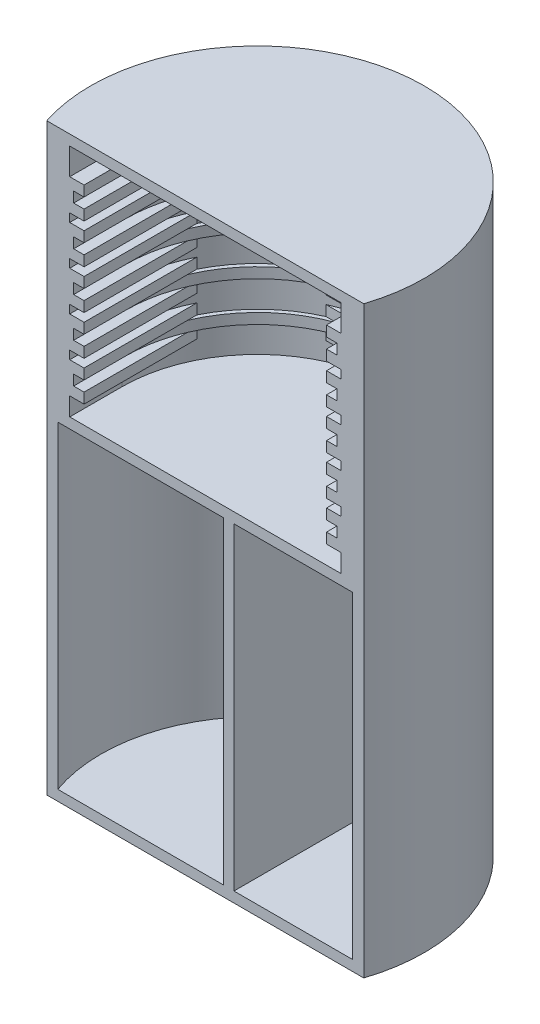
SolidWorks part; units mm, degrees
ref_plane "Front Plane" through (0, 0, 0) normal (0, 0, 1) x (1, 0, 0)
ref_plane "Top Plane" through (0, 0, 0) normal (0, 1, 0) x (1, 0, 0)
ref_plane "Right Plane" through (0, 0, 0) normal (1, 0, 0) x (0, 0, -1)
ref_plane "HYDRA SECTION TOP" through (0, 22.5, 0) normal (0, 1, 0) x (1, 0, 0)
ref_plane "HYDRA SECTION BOTTOM" through (0, -22.5, 0) normal (0, 1, 0) x (1, 0, 0)
ref_plane "BATTERY SECTION BOTTOM" through (0, -87.5, 0) normal (0, 1, 0) x (1, 0, 0)
sketch "Sketch1" plane through (0, 0, 0) normal (0, 1, 0) x (1, 0, 0)
  line L0 (-26, 0) -> (-26, -10)
  line L1 (26, 0) -> (26, -10)
  line L2 (-26, -10) -> (-30.3974, -10)
  line L3 (26, -10) -> (30.3974, -10)
  arc A0 (26, 0) -> (-26, 0) centre (0, 0) ccw
  arc A1 (30.3974, -10) -> (-30.3974, -10) centre (0, 0) ccw
  circle A2 centre (0, 0) radius 32 construction
  circle A3 centre (0, 0) radius 26 construction
  dimension "D1" = 52
  dimension "D2" = 64
  dimension "D3" = 10
extrude "BULK EXTRUDE" add sketch "Sketch1" along normal up to surface (22.5 mm away) and the other way up to surface (22.5 mm away) up to plane "HYDRA SECTION TOP" other way up to plane "HYDRA SECTION BOTTOM"
sketch "Sketch3" plane through (0, 0, 0) normal (0, 0, 1) x (1, 0, 0)
  line L0 (-25.25, 0.2) -> (-23.25, 0.2)
  line L1 (-23.25, 0.2) -> (-23.25, 2.2)
  line L2 (-23.25, 2.2) -> (-26.25, 2.2)
  line L3 (-26.25, 2.2) -> (-26.25, -3.8)
  line L4 (-26.25, -3.8) -> (-23.25, -3.8)
  line L5 (-23.25, -3.8) -> (-23.25, -1.8)
  line L6 (-23.25, -1.8) -> (-25.25, -1.8)
  line L7 (-25.25, -1.8) -> (-25.25, 0.2)
  line L8 (-26.25, -0.8) -> (-25.25, -0.8) construction
  line L9 (0, -23.1) -> (0, 23.1) construction
  line L10 (25.25, -1.8) -> (25.25, 0.2)
  line L11 (23.25, -1.8) -> (25.25, -1.8)
  line L12 (23.25, -3.8) -> (23.25, -1.8)
  line L13 (26.25, -3.8) -> (23.25, -3.8)
  line L14 (26.25, 2.2) -> (26.25, -3.8)
  line L15 (23.25, 2.2) -> (26.25, 2.2)
  line L16 (23.25, 0.2) -> (23.25, 2.2)
  line L17 (25.25, 0.2) -> (23.25, 0.2)
  line L18 (-25.25, 7.8) -> (-23.25, 7.8)
  line L19 (-23.25, 7.8) -> (-23.25, 9.8)
  line L20 (-23.25, 9.8) -> (-26.25, 9.8)
  line L21 (-26.25, 9.8) -> (-26.25, 3.8)
  line L22 (-26.25, 3.8) -> (-23.25, 3.8)
  line L23 (-23.25, 3.8) -> (-23.25, 5.8)
  line L24 (-23.25, 5.8) -> (-25.25, 5.8)
  line L25 (-25.25, 5.8) -> (-25.25, 7.8)
  line L26 (25.25, 5.8) -> (25.25, 7.8)
  line L27 (25.25, 7.8) -> (23.25, 7.8)
  line L28 (23.25, 7.8) -> (23.25, 9.8)
  line L29 (23.25, 9.8) -> (26.25, 9.8)
  line L30 (26.25, 9.8) -> (26.25, 3.8)
  line L31 (26.25, 3.8) -> (23.25, 3.8)
  line L32 (23.25, 3.8) -> (23.25, 5.8)
  line L33 (23.25, 5.8) -> (25.25, 5.8)
  line L34 (-25.25, 15.4) -> (-23.25, 15.4)
  line L35 (-23.25, 15.4) -> (-23.25, 17.4)
  line L36 (-23.25, 17.4) -> (-26.25, 17.4)
  line L37 (-26.25, 17.4) -> (-26.25, 11.4)
  line L38 (-26.25, 11.4) -> (-23.25, 11.4)
  line L39 (-23.25, 11.4) -> (-23.25, 13.4)
  line L40 (-23.25, 13.4) -> (-25.25, 13.4)
  line L41 (-25.25, 13.4) -> (-25.25, 15.4)
  line L42 (25.25, 13.4) -> (25.25, 15.4)
  line L43 (25.25, 15.4) -> (23.25, 15.4)
  line L44 (23.25, 15.4) -> (23.25, 17.4)
  line L45 (23.25, 17.4) -> (26.25, 17.4)
  line L46 (26.25, 17.4) -> (26.25, 11.4)
  line L47 (26.25, 11.4) -> (23.25, 11.4)
  line L48 (23.25, 11.4) -> (23.25, 13.4)
  line L49 (23.25, 13.4) -> (25.25, 13.4)
  line L50 (-25.25, -7.4) -> (-23.25, -7.4)
  line L51 (-23.25, -7.4) -> (-23.25, -5.4)
  line L52 (-23.25, -5.4) -> (-26.25, -5.4)
  line L53 (-26.25, -5.4) -> (-26.25, -11.4)
  line L54 (-26.25, -11.4) -> (-23.25, -11.4)
  line L55 (-23.25, -11.4) -> (-23.25, -9.4)
  line L56 (-23.25, -9.4) -> (-25.25, -9.4)
  line L57 (-25.25, -9.4) -> (-25.25, -7.4)
  line L58 (25.25, -9.4) -> (25.25, -7.4)
  line L59 (25.25, -7.4) -> (23.25, -7.4)
  line L60 (23.25, -7.4) -> (23.25, -5.4)
  line L61 (23.25, -5.4) -> (26.25, -5.4)
  line L62 (26.25, -5.4) -> (26.25, -11.4)
  line L63 (26.25, -11.4) -> (23.25, -11.4)
  line L64 (23.25, -11.4) -> (23.25, -9.4)
  line L65 (23.25, -9.4) -> (25.25, -9.4)
  line L66 (-25.25, -15) -> (-23.25, -15)
  line L67 (-23.25, -15) -> (-23.25, -13)
  line L68 (-23.25, -13) -> (-26.25, -13)
  line L69 (-26.25, -13) -> (-26.25, -19)
  line L70 (-26.25, -19) -> (-23.25, -19)
  line L71 (-23.25, -19) -> (-23.25, -17)
  line L72 (-23.25, -17) -> (-25.25, -17)
  line L73 (-25.25, -17) -> (-25.25, -15)
  line L74 (25.25, -17) -> (25.25, -15)
  line L75 (25.25, -15) -> (23.25, -15)
  line L76 (23.25, -15) -> (23.25, -13)
  line L77 (23.25, -13) -> (26.25, -13)
  line L78 (26.25, -13) -> (26.25, -19)
  line L79 (26.25, -19) -> (23.25, -19)
  line L80 (23.25, -19) -> (23.25, -17)
  line L81 (23.25, -17) -> (25.25, -17)
  dimension "D1" = 23.25
  dimension "D2" = 2
  dimension "D3" = 2
  dimension "D4" = 6
  dimension "D5" = 1
  dimension "D8" = 7.6
  dimension "D9" = 7.6
  dimension "D10" = 0.8
  dimension "D6" = 3
  dimension "D7" = 3
extrude "SIDE CRADDLES" add sketch "Sketch3" along normal blind 10 and the other way up to surface other way up to face at (0, 0, -13)
sketch "Sketch5" plane through (0, 0, 0) normal (1, 0, 0) x (0, 0, -1)
  line L0 (23.75, 2.2) -> (23.75, 0.2)
  line L1 (23.75, 0.2) -> (25.25, 0.2)
  line L2 (25.25, 0.2) -> (25.25, -1.8)
  line L3 (25.25, -1.8) -> (23.75, -1.8)
  line L4 (23.75, -1.8) -> (23.75, -3.8)
  line L5 (23.75, -3.8) -> (26.25, -3.8)
  line L6 (26.25, -3.8) -> (26.25, 2.2)
  line L7 (26.25, 2.2) -> (23.75, 2.2)
  line L8 (25.25, -0.8) -> (26.25, -0.8) construction
  line L9 (26.25, 9.8) -> (23.75, 9.8)
  line L10 (23.75, 9.8) -> (23.75, 7.8)
  line L11 (23.75, 7.8) -> (25.25, 7.8)
  line L12 (25.25, 7.8) -> (25.25, 5.8)
  line L13 (25.25, 5.8) -> (23.75, 5.8)
  line L14 (23.75, 5.8) -> (23.75, 3.8)
  line L15 (23.75, 3.8) -> (26.25, 3.8)
  line L16 (26.25, 3.8) -> (26.25, 9.8)
  line L17 (26.25, 17.4) -> (23.75, 17.4)
  line L18 (23.75, 17.4) -> (23.75, 15.4)
  line L19 (23.75, 15.4) -> (25.25, 15.4)
  line L20 (25.25, 15.4) -> (25.25, 13.4)
  line L21 (25.25, 13.4) -> (23.75, 13.4)
  line L22 (23.75, 13.4) -> (23.75, 11.4)
  line L23 (23.75, 11.4) -> (26.25, 11.4)
  line L24 (26.25, 11.4) -> (26.25, 17.4)
  line L25 (26.25, -5.4) -> (23.75, -5.4)
  line L26 (23.75, -5.4) -> (23.75, -7.4)
  line L27 (23.75, -7.4) -> (25.25, -7.4)
  line L28 (25.25, -7.4) -> (25.25, -9.4)
  line L29 (25.25, -9.4) -> (23.75, -9.4)
  line L30 (23.75, -9.4) -> (23.75, -11.4)
  line L31 (23.75, -11.4) -> (26.25, -11.4)
  line L32 (26.25, -11.4) -> (26.25, -5.4)
  line L33 (26.25, -13) -> (23.75, -13)
  line L34 (23.75, -13) -> (23.75, -15)
  line L35 (23.75, -15) -> (25.25, -15)
  line L36 (25.25, -15) -> (25.25, -17)
  line L37 (25.25, -17) -> (23.75, -17)
  line L38 (23.75, -17) -> (23.75, -19)
  line L39 (23.75, -19) -> (26.25, -19)
  line L40 (26.25, -19) -> (26.25, -13)
  point P2 (25.25, -0.8)
  dimension "D1" = 2
  dimension "D2" = 6
  dimension "D3" = 1.5
  dimension "D4" = 1
  dimension "D5" = 25.25
  dimension "D8" = 7.6
  dimension "D9" = 7.6
  dimension "D6" = 3
  dimension "D7" = 3
extrude "FRONT CRADDLE" add sketch "Sketch5" along normal up to next and the other way up to next
sketch "Sketch6" plane through (0, 0, 0) normal (0, 0, 1) x (1, 0, 0)
  line L0 (0, 0) -> (0, 20) construction
  line L1 (-23.25, -1.8) -> (-25.25, -1.8) construction
  line L2 (-25.25, 0.2) -> (-26.25, 0.2)
  line L3 (-25.25, 0.2) -> (-25.25, -1.8)
  line L4 (-25.25, -1.8) -> (-26.25, -1.8)
  line L5 (-26.25, 0.2) -> (-26.25, -1.8)
  line L6 (-26.25, 2.2) -> (-26.25, -3.8) construction
  line L7 (-25.25, 7.8) -> (-25.25, 5.8)
  line L8 (-25.25, 7.8) -> (-26.25, 7.8)
  line L9 (-26.25, 7.8) -> (-26.25, 5.8)
  line L10 (-25.25, 5.8) -> (-26.25, 5.8)
  line L11 (-25.25, 15.4) -> (-25.25, 13.4)
  line L12 (-25.25, 15.4) -> (-26.25, 15.4)
  line L13 (-26.25, 15.4) -> (-26.25, 13.4)
  line L14 (-25.25, 13.4) -> (-26.25, 13.4)
  line L15 (-25.25, -7.4) -> (-25.25, -9.4)
  line L16 (-25.25, -7.4) -> (-26.25, -7.4)
  line L17 (-26.25, -7.4) -> (-26.25, -9.4)
  line L18 (-25.25, -9.4) -> (-26.25, -9.4)
  line L19 (-25.25, -15) -> (-25.25, -17)
  line L20 (-25.25, -15) -> (-26.25, -15)
  line L21 (-26.25, -15) -> (-26.25, -17)
  line L22 (-25.25, -17) -> (-26.25, -17)
  dimension "D1" = 20
  dimension "D2" = 3
  dimension "D4" = 7.6
  dimension "D5" = 7.6
  dimension "D3" = 3
revolve "PCB CRADDLE ROUNDENING EXTENSION" add sketch "Sketch6" angle 180 about L0 reverse direction yes
sketch "Sketch7" plane through (0, -22.5, 0) normal (0, 1, 0) x (1, 0, 0)
  line L0 (-30.3974, -10) -> (30.3974, -10)
  arc A0 (30.3974, -10) -> (-30.3974, -10) centre (0, 0) ccw construction
  arc A1 (30.3974, -10) -> (-30.3974, -10) centre (0, 0) ccw
extrude "BATTERY SECTION TOP" add sketch "Sketch7" against normal blind 2
sketch "Sketch8" plane through (0, -22.5, 0) normal (0, 1, 0) x (1, 0, 0)
  line L0 (3.5, 29.7951) -> (3.5, -10)
  line L1 (3.5, -10) -> (5.5, -10)
  line L2 (5.5, -10) -> (5.5, 29.4915)
  line L4 (-26, -10) -> (-26, 0)
  line L5 (-30.3974, -10) -> (-26, -10)
  line L6 (26, -10) -> (30.3974, -10)
  line L7 (26, 0) -> (26, -10)
  line L9 (-30.3974, -10) -> (-28.2843, -10)
  line L10 (28.2843, -10) -> (30.3974, -10)
  arc A0 (28.2843, -10) -> (5.5, 29.4915) centre (0, 0) ccw
  arc A1 (3.5, 29.7951) -> (-28.2843, -10) centre (0, 0) ccw
  arc A2 (30.3974, -10) -> (-30.3974, -10) centre (0, 0) ccw
  arc A3 (26, 0) -> (-26, 0) centre (0, 0) ccw
  arc A4 (30.3974, -10) -> (-30.3974, -10) centre (0, 0) ccw
  dimension "D2" = 2
  dimension "D3" = 3.5
  dimension "D4" = 2
  dimension "D1" = 0
extrude "BATTERY SECTION WALLS" add sketch "Sketch8" against normal up to surface (65 mm away) up to plane "BATTERY SECTION BOTTOM"
sketch "Sketch9" plane through (0, -87.5, 0) normal (0, 1, 0) x (1, 0, 0)
  line L1 (-30.3974, -10) -> (30.3974, -10)
  line L2 (-30.3974, -10) -> (30.3974, -10)
  arc A1 (30.3974, -10) -> (-30.3974, -10) centre (0, 0) ccw
  arc A2 (30.3974, -10) -> (-30.3974, -10) centre (0, 0) ccw
  dimension "D1" = 0
extrude "BATTERY SECTION FLOOR" add sketch "Sketch9" along normal blind 2
sketch "Sketch10" plane through (0, 22.5, 0) normal (0, 1, 0) x (1, 0, 0)
  line L1 (-30.3974, -10) -> (30.3974, -10)
  line L2 (-30.3974, -10) -> (30.3974, -10)
  arc A1 (30.3974, -10) -> (-30.3974, -10) centre (0, 0) ccw
  arc A2 (30.3974, -10) -> (-30.3974, -10) centre (0, 0) ccw
  dimension "D1" = 0
extrude "ANTENNA BAY FLOOR" add sketch "Sketch10" along normal blind 2
